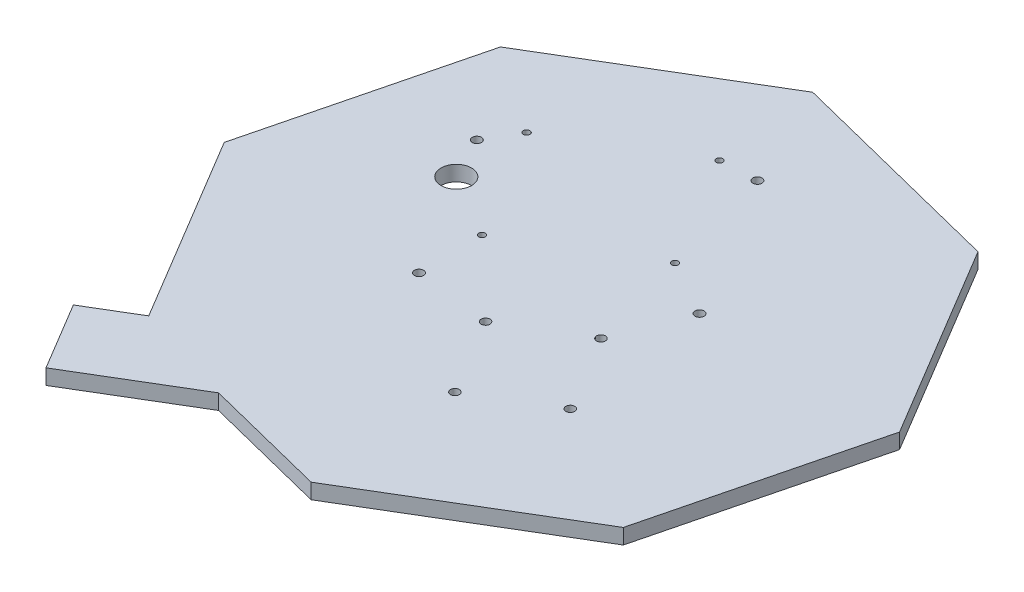
SolidWorks part; units mm, degrees
ref_plane "Front Plane" through (0, 0, 0) normal (0, 0, 1) x (1, 0, 0)
ref_plane "Top Plane" through (0, 0, 0) normal (0, 1, 0) x (1, 0, 0)
ref_plane "Right Plane" through (0, 0, 0) normal (1, 0, 0) x (0, 0, -1)
sketch "Sketch1" plane through (0, 0, 0) normal (0, 1, 0) x (1, 0, 0)
  line L1 (73.765, 99.3213) -> (-18.0711, 122.3905)
  line L2 (-18.0711, 122.3905) -> (-99.3213, 73.765)
  line L3 (-99.3213, 73.765) -> (-122.3905, -18.0711)
  line L4 (-122.3905, -18.0711) -> (-73.765, -99.3213)
  line L5 (-73.765, -99.3213) -> (18.0711, -122.3905)
  line L6 (18.0711, -122.3905) -> (99.3213, -73.765)
  line L7 (99.3213, -73.765) -> (122.3905, 18.0711)
  line L8 (122.3905, 18.0711) -> (73.765, 99.3213)
  circle A0 centre (0, 0) radius 114.3 construction
  dimension "baselength" = 228.6
extrude "Boss-Extrude2" add sketch "Sketch1" along normal blind 6.35
sketch "Sketch2" plane through (0, 6.35, 0) normal (0, 1, 0) x (-1, 0, 0)
  line L0 (75.5911, 96.27) -> (95.2066, 108.0093)
  line L1 (122.3905, 18.0711) -> (73.765, 99.3213) construction
  line L2 (95.2066, 108.0093) -> (78.2499, 136.3429)
  line L3 (78.2499, 136.3429) -> (33.3521, 109.473)
  line L4 (73.765, 99.3213) -> (-18.0711, 122.3905) construction
  line L5 (73.765, 99.3213) -> (75.5911, 96.27)
  line L6 (73.765, 99.3213) -> (33.3521, 109.473)
  dimension "D1" = 22.86
  dimension "D2" = 3.556
  dimension "D3" = 33.02
extrude "Boss-Extrude3" add sketch "Sketch2" against normal blind 6.35
sketch "Sketch3" plane through (0, 0, 0) normal (0, -1, 0) x (1, 0, 0)
  line L28 (122.3905, -18.0711) -> (99.3213, 73.765)
  circle A0 centre (-63.0561, -48.3878) radius 1.3716 construction
  circle A1 centre (-35.4167, -2.2041) radius 1.3716 construction
  circle A2 centre (14.7948, -32.2539) radius 1.3716 construction
  circle A3 centre (-12.8446, -78.4376) radius 1.3716 construction
  circle A4 centre (-63.0561, -48.3878) radius 1.3716
  circle A5 centre (-35.4167, -2.2041) radius 1.3716
  circle A6 centre (14.7948, -32.2539) radius 1.3716
  circle A7 centre (-12.8446, -78.4376) radius 1.3716
extrude "Cut-Extrude1" cut sketch "Sketch3" against normal through all contours A7 | A5 | A4 | A6 region at (-35.4167, 0, -2.2041) region at (-12.8446, 0, -78.4376)
sketch "Sketch4" plane through (0, 0, 0) normal (0, -1, 0) x (1, 0, 0)
  circle A0 centre (-61.7374, -17.8145) radius 6.35 construction
  circle A1 centre (-61.7374, -17.8145) radius 6.35
extrude "Cut-Extrude2" cut sketch "Sketch4" against normal through all
sketch "Sketch5" plane through (0, 0, 0) normal (0, -1, 0) x (1, 0, 0)
  circle A0 centre (2.2673, -79.0601) radius 1.905 construction
  circle A1 centre (-70.7462, -35.364) radius 1.905 construction
  circle A2 centre (38.1372, -19.1237) radius 1.905 construction
  circle A3 centre (-34.8763, 24.5724) radius 1.905 construction
  circle A4 centre (2.2673, -79.0601) radius 1.905
  circle A5 centre (-70.7462, -35.364) radius 1.905
  circle A6 centre (38.1372, -19.1237) radius 1.905
  circle A7 centre (-34.8763, 24.5724) radius 1.905
extrude "Cut-Extrude3" cut sketch "Sketch5" against normal through all
sketch "Sketch7" plane through (0, 6.35, 0) normal (0, 1, 0) x (1, 0, 0)
  circle A0 centre (15.5386, -60.0421) radius 1.85 construction
  circle A1 centre (-3.4619, -28.2934) radius 1.85 construction
  circle A2 centre (26.5707, -10.3199) radius 1.85 construction
  circle A3 centre (45.5712, -42.0686) radius 1.85 construction
  circle A4 centre (15.5386, -60.0421) radius 1.85
  circle A5 centre (-3.4619, -28.2934) radius 1.85
  circle A6 centre (26.5707, -10.3199) radius 1.85
  circle A7 centre (45.5712, -42.0686) radius 1.85
extrude "Cut-Extrude4" cut sketch "Sketch7" against normal through all
equation "\"baselength\"=9"
equation "\"material\"=\"GMaterial@Platform.assembly\""
equation "\"D1@Boss-Extrude2\" = \"material\""
equation "\"D1@Boss-Extrude3\" = \"material\""
